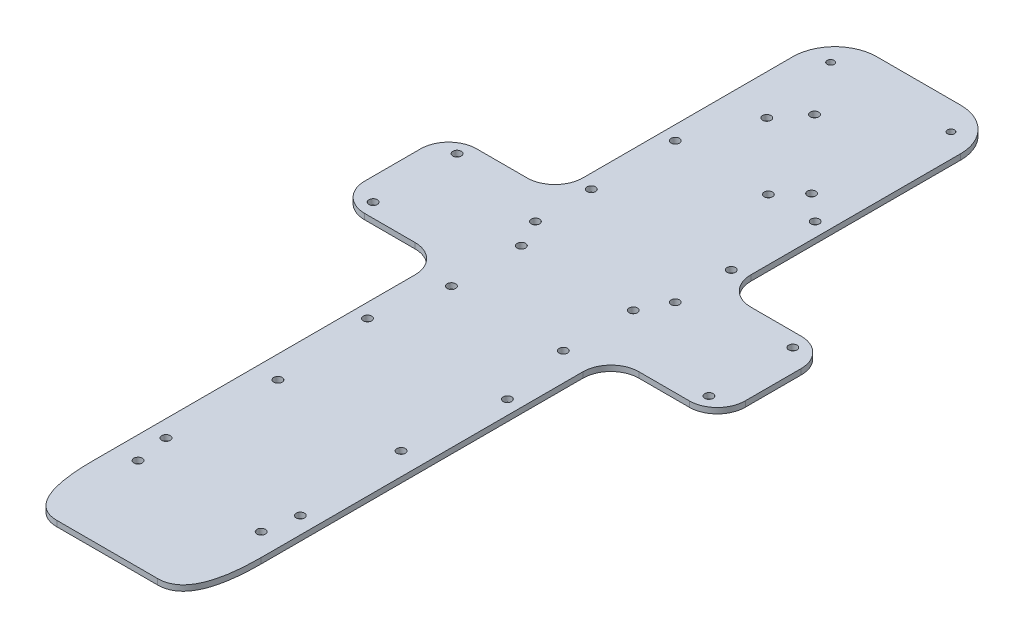
SolidWorks part; units mm, degrees
ref_plane "Спереди" through (0, 0, 0) normal (0, 0, 1) x (1, 0, 0)
ref_plane "Сверху" through (0, 0, 0) normal (0, 1, 0) x (1, 0, 0)
ref_plane "Справа" through (0, 0, 0) normal (1, 0, 0) x (0, 0, -1)
sketch "Эскиз1" plane through (0, 0, 0) normal (0, 1, 0) x (1, 0, 0)
  line L0 (0, 160) -> (0, -130) construction
  line L1 (-30, 160) -> (30, 160)
  line L2 (-30, 160) -> (-30, -130)
  line L3 (-30, -130) -> (30, -130)
  line L4 (30, 160) -> (30, -130)
  line L5 (-30, 0) -> (30, 0) construction
  dimension "D1" = 60
  dimension "D2" = 160
  dimension "D3" = 130
extrude "тело" add sketch "Эскиз1" along normal blind 2
sketch "Эскиз3" plane through (0, 2, 0) normal (0, 1, 0) x (1, 0, 0)
  line L0 (0, 160) -> (0, -130) construction
  line L1 (30, 160) -> (-30, 160) construction
  line L2 (-30, -130) -> (30, -130) construction
  line L3 (-30, 160) -> (-30, -130) construction
  line L4 (-30, 60) -> (-68, 60)
  line L5 (-30, 60) -> (-30, 20)
  line L6 (-30, 20) -> (-68, 20)
  line L7 (-68, 60) -> (-68, 20)
  line L8 (30, -130) -> (30, 160) construction
  line L9 (30, 60) -> (68, 60)
  line L10 (30, 60) -> (30, 20)
  line L11 (30, 20) -> (68, 20)
  line L12 (68, 60) -> (68, 20)
  line L13 (-68, 40) -> (68, 40) construction
  dimension "D1" = 40
  dimension "D2" = 40
  dimension "D3" = 68
sketch "Эскиз4" plane through (0, 2, 0) normal (0, 1, 0) x (1, 0, 0)
  line L0 (0, 160) -> (0, -130) construction
  line L1 (-60, 55) -> (-60, 25) construction
  line L2 (60, 55) -> (60, 25) construction
  line L3 (-60, 40) -> (60, 40) construction
  circle A0 centre (-60, 55) radius 1.5
  circle A1 centre (-60, 25) radius 1.5
  circle A2 centre (60, 55) radius 1.5
  circle A3 centre (60, 25) radius 1.5
  point P15 (0, 40)
  dimension "D1" = 3
  dimension "D2" = 30
  dimension "D3" = 60
  dimension "D4" = 40
extrude "уши крепления подвески" add sketch "Эскиз3" against normal up to surface (2 mm away) up to face at (0, 0, -15)
extrude "крепление подвески" cut sketch "Эскиз4" against normal through all
sketch "Эскиз6" plane through (0, 2, 0) normal (0, 1, 0) x (1, 0, 0)
  line L0 (-22, -47) -> (-22, -97) construction
  line L1 (-22, -47) -> (22, -47) construction
  line L2 (-30, -130) -> (30, -130) construction
  line L3 (-22, -97) -> (22, -97) construction
  line L4 (22, -97) -> (22, -47) construction
  circle A0 centre (-22, -47) radius 1.5
  circle A1 centre (22, -47) radius 1.5
  circle A2 centre (22, -97) radius 1.5
  circle A3 centre (-22, -97) radius 1.5
  point P2 (0, -97)
  point P12 (0, -47)
  dimension "D1" = 3
  dimension "D2" = 33
  dimension "D3" = 44
  dimension "D4" = 50
extrude "крепление bullet" cut sketch "Эскиз6" against normal through all
sketch "Эскиз8" plane through (0, 2, 0) normal (0, 1, 0) x (1, 0, 0)
  circle A0 centre (-20, -130) radius 1.5
  circle A1 centre (20, -130) radius 1.5
  dimension "D1" = 3
extrude "крепление камеры" [suppressed] cut sketch "Эскиз8" against normal through all and the other way through all
sketch "Эскиз11" plane through (0, 2, 0) normal (0, 1, 0) x (1, 0, 0)
  line L0 (0, 160) -> (0, -130) construction
  line L1 (30, 160) -> (-30, 160) construction
  line L2 (-30, -130) -> (30, -130) construction
  line L3 (-30, 15) -> (30, 15) construction
  line L6 (-25, 135) -> (25, 135) construction
  line L7 (-25, -96) -> (25, -96) construction
  line L8 (-30, 20) -> (-30, -130) construction
  line L9 (30, -130) -> (30, 20) construction
  circle A0 centre (-25, 135) radius 1.5
  circle A1 centre (25, 135) radius 1.5
  circle A2 centre (-25, -96) radius 1.5
  circle A3 centre (25, -96) radius 1.5
  point P21 (0, -96)
  point P22 (0, 135)
  point P23 (0, 15)
  dimension "D1" = 3
  dimension "D2" = 50
  dimension "D3" = 120
  dimension "D4" = 111
extrude "крепление нижнего этажа" [suppressed] cut sketch "Эскиз11" against normal through all
sketch "Эскиз15" plane through (0, 2, 0) normal (0, 1, 0) x (1, 0, 0)
  line L0 (0, 160) -> (0, -130) construction
  line L1 (-25, 125) -> (25, 125) construction
  line L2 (-25, -10) -> (25, -10) construction
  line L3 (-25, -85) -> (25, -85) construction
  line L5 (30, 160) -> (-30, 160) construction
  line L6 (-30, -130) -> (30, -130) construction
  line L8 (-30, 15) -> (30, 15) construction
  line L10 (-30, 20) -> (-30, -130) construction
  line L11 (30, -130) -> (30, 20) construction
  circle A0 centre (-25, 125) radius 1.5
  circle A1 centre (25, 125) radius 1.5
  circle A2 centre (25, -85) radius 1.5
  circle A3 centre (-25, -85) radius 1.5
  circle A4 centre (25, -10) radius 1.5
  circle A5 centre (-25, -10) radius 1.5
  point P20 (0, 15)
  point P21 (0, 15)
  point P22 (0, 125)
  point P23 (0, -85)
  point P28 (0, -10)
  dimension "D1" = 3
  dimension "D5" = 3
  dimension "D2" = 50
  dimension "D3" = 110
  dimension "D4" = 100
  dimension "D6" = 25
extrude "крепление уголков" [suppressed] cut sketch "Эскиз15" against normal through all
sketch "Эскиз19" plane through (0, 0, 0) normal (0, -1, 0) x (1, 0, 0)
  line L1 (-25, 12) -> (25, 12) construction
  line L2 (-25, 12) -> (-25, -48) construction
  line L3 (-25, -48) -> (25, -48) construction
  line L4 (25, 12) -> (25, -48) construction
  line L5 (-25, 12) -> (25, -48) construction
  line L6 (-25, -48) -> (25, 12) construction
  circle A0 centre (-25, 12) radius 1.5
  circle A1 centre (25, 12) radius 1.5
  circle A2 centre (25, -48) radius 1.5
  circle A3 centre (-25, -48) radius 1.5
  circle A7 centre (22, 47) radius 1.5 construction
  point P0 (0, -18)
  dimension "D3" = 3
  dimension "D4" = 35
  dimension "D1" = 50
  dimension "D2" = 60
extrude "Крепление аккумулятора" cut sketch "Эскиз19" against normal through all
fillet "Скругление3" radius 15 2 edges at (-30, 1, -160) (30, 1, -160)
sketch "Эскиз20" plane through (0, 0, 0) normal (0, -1, 0) x (1, 0, 0)
  line L1 (-20, -13) -> (20, -13) construction
  line L2 (-20, -13) -> (-20, -38) construction
  line L3 (-20, -38) -> (20, -38) construction
  line L4 (20, -13) -> (20, -38) construction
  circle A0 centre (-20, -13) radius 1.5
  circle A1 centre (20, -13) radius 1.5
  circle A2 centre (-20, -38) radius 1.5
  circle A3 centre (20, -38) radius 1.5
  circle A4 centre (22, 47) radius 1.5 construction
  point P4 (0, -13)
  dimension "D3" = 3
  dimension "D1" = 40
  dimension "D2" = 25
  dimension "D4" = 60
extrude "Крепление платы раздачи питания" cut sketch "Эскиз20" against normal up to next contours A0 | A1 | A2 | A3 region at (-20, 0, -13) region at (20, 0, -13) region at (-20, 0, -38) region at (20, 0, -38)
sketch "Эскиз21" plane through (0, 0, 0) normal (0, -1, 0) x (1, 0, 0)
  line L1 (-25, -68) -> (25, -68) construction
  line L2 (-25, -68) -> (-25, -98) construction
  line L3 (-25, -98) -> (25, -98) construction
  line L4 (25, -68) -> (25, -98) construction
  circle A0 centre (-25, -68) radius 1.5
  circle A1 centre (25, -68) radius 1.5
  circle A2 centre (25, -98) radius 1.5
  circle A3 centre (-25, -98) radius 1.5
  circle A6 centre (20, -38) radius 1.5 construction
  point P9 (0, -68)
  dimension "D1" = 3
  dimension "D4" = 30
  dimension "D2" = 50
  dimension "D3" = 30
extrude "Крепление держателя драйверов двигателей" cut sketch "Эскиз21" against normal up to next
sketch "Эскиз7" plane through (0, 2, 0) normal (0, 1, 0) x (1, 0, 0)
  line L1 (-15.7, 121.4) -> (15.7, 121.4) construction
  line L2 (-15.7, 121.4) -> (-15.7, 106) construction
  line L3 (-15.7, 106) -> (15.7, 106) construction
  line L4 (15.7, 121.4) -> (15.7, 106) construction
  circle A0 centre (-15.7, 121.4) radius 1.5
  circle A1 centre (25, 98) radius 1.5 construction
  circle A2 centre (15.7, 106) radius 1.5
  point P12 (0, 106)
  dimension "D1" = 3
  dimension "D4" = 8
  dimension "D2" = 31.4
  dimension "D3" = 15.4
extrude "крепление р-ра питания серв" cut sketch "Эскиз7" against normal through all
sketch "Эскиз22" plane through (0, 0, 0) normal (0, -1, 0) x (1, 0, 0)
  line L1 (-8.25, -98) -> (8.25, -98) construction
  line L2 (-8.25, -98) -> (-8.25, -131) construction
  line L3 (-8.25, -131) -> (8.25, -131) construction
  line L4 (8.25, -98) -> (8.25, -131) construction
  line L5 (-8.25, -98) -> (8.25, -131) construction
  line L6 (-8.25, -131) -> (8.25, -98) construction
  circle A8 centre (25, -48) radius 1.5 construction
  circle A9 centre (8.25, -98) radius 1.5
  circle A10 centre (-8.25, -131) radius 1.5
  point P0 (0, -98)
  dimension "D3" = 50
  dimension "D4" = 3
  dimension "D1" = 16.5
  dimension "D2" = 33
extrude "Крепление р-ра питания светодиодами" cut sketch "Эскиз22" against normal up to next
sketch "Эскиз23" plane through (0, 2, 0) normal (0, 1, 0) x (1, 0, 0)
  line L0 (-21.5, 150) -> (21.5, 150) construction
  line L1 (15, 160) -> (-15, 160) construction
  circle A0 centre (-21.5, 150) radius 1.25
  circle A1 centre (21.5, 150) radius 1.25
  point P4 (0, 150)
  point P7 (0, 160)
  dimension "D1" = 2.5
  dimension "D2" = 43
  dimension "D3" = 10
extrude "Крепление фронтальной камеры" cut sketch "Эскиз23" against normal up to next
sketch "Эскиз24" plane through (0, 2, 0) normal (0, 1, 0) x (1, 0, 0)
  line L0 (0, -130) -> (0, 160) construction
  line L1 (-30, -130) -> (30, -130) construction
  line L2 (15, 160) -> (-15, 160) construction
  line L4 (-30, 20) -> (-30, -130) construction
  circle A0 centre (-24, -85) radius 1.5
  circle A2 centre (24, -85) radius 1.5
  dimension "D1" = 3
  dimension "D2" = 45
  dimension "D3" = 6
extrude "Крепление силовых уголков в задней части" cut sketch "Эскиз24" against normal up to next
fillet "Скругление4" radius 25 1 edges at (-30, 1, 130) second distance 12 conic rho 0.5 first distance on face at (-30, 1, 55)
fillet "Скругление5" radius 12 1 edges at (30, 1, 130) second distance 25 conic rho 0.5 first distance on face at (-6, 1.25, 130)
fillet "Скругление6" radius 10 8 edges at (-30, 1, -20) (30, 1, -20) (-30, 1, -60) (30, 1, -60) (68, 1, -20) (68, 1, -60) (-68, 1, -20) (-68, 1, -60)
